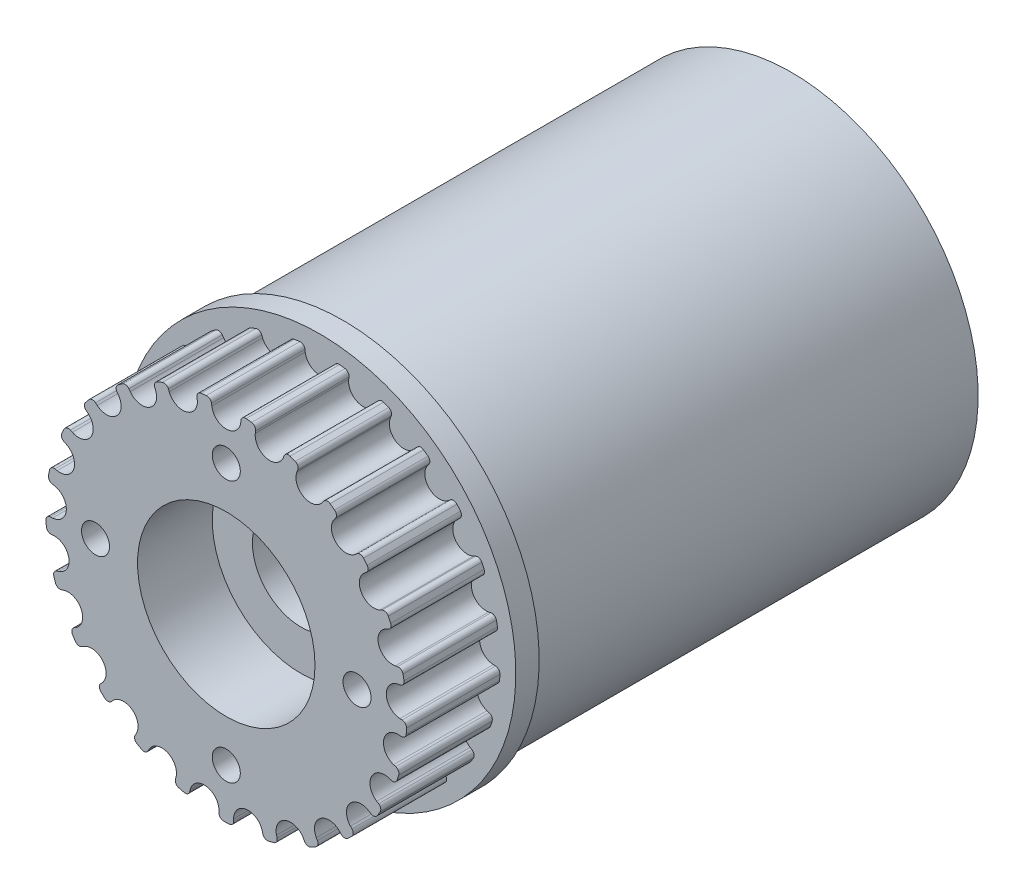
SolidWorks part; units mm, degrees
material "6061 合金"
ref_plane "前视基准面" through (0, 0, 0) normal (0, 0, 1) x (1, 0, 0)
ref_plane "上视基准面" through (0, 0, 0) normal (0, 1, 0) x (1, 0, 0)
ref_plane "右视基准面" through (0, 0, 0) normal (1, 0, 0) x (0, 0, -1)
other "Configuration Table"
sketch "草图1" plane through (0, 0, 0) normal (0, 0, 1) x (1, 0, 0)
  circle A0 centre (0, 0) radius 19.8944
  dimension "P.D" = 39.7887
extrude "凸台-拉伸1" add sketch "草图1" along normal blind 68.5
sketch "草图2" plane through (0, 0, 68.5) normal (0, 0, 1) x (1, 0, 0)
  line L0 (0, 19.8944) -> (0, 19.3224) construction
  line L1 (0, 19.3224) -> (0, 0) construction
  line L2 (1.5774, 18.7687) -> (1.5484, 18.5323)
  line L3 (2.4934, 19.7375) -> (2.4217, 19.17)
  line L4 (-2.4934, 19.7375) -> (-2.4217, 19.17)
  line L5 (-1.5774, 18.7687) -> (-1.5484, 18.5323)
  circle A0 centre (0, 0) radius 19.8944 construction
  arc A1 (2.4934, 19.7375) -> (-2.4934, 19.7375) centre (0, 0) ccw
  circle A2 centre (0, 0) radius 19.3224 construction
  arc A3 (-1.5484, 18.5323) -> (1.5484, 18.5323) centre (0, 18.7224) ccw
  arc A4 (2.1288, 19.2047) -> (2.4217, 19.17) centre (0, 0) cw
  arc A5 (1.5774, 18.7687) -> (2.1288, 19.2047) centre (2.0737, 18.7078) cw
  arc A6 (-1.5774, 18.7687) -> (-2.1288, 19.2047) centre (-2.0737, 18.7078) ccw
  arc A7 (-2.1288, 19.2047) -> (-2.4217, 19.17) centre (0, 0) ccw
  point P16 (1.6369, 19.2529)
  point P21 (0, 17.1624)
  dimension "R" = 1.56
  dimension "D3" = 0.5
  dimension "D1" = 7.2
  dimension "D2" = 7
  dimension "H_g" = 2.16
  dimension "delta" = 0.572
extrude "切除-拉伸1" cut sketch "草图2" against normal through all
pattern_circular "阵列(圆周)1" count 25 over 360 about axis through (0, 0, 68.5) along (0, 0, -1) of "切除-拉伸1" reverse direction yes
ref_plane "基准面1" through (0, 0, 10) normal (0, 0, -1) x (-1, 0, 0)
ref_plane "基准面2" through (0, 0, 11) normal (0, 0, -1) x (-1, 0, 0)
ref_plane "基准面3" through (0, 0, 56) normal (0, 0, -1) x (-1, 0, 0)
ref_plane "基准面4" through (0, 0, 57.5) normal (0, 0, -1) x (-1, 0, 0)
ref_plane "基准面5" through (0, 0, 58.5) normal (0, 0, -1) x (-1, 0, 0)
sketch "草图3" plane through (0, 0, 10) normal (0, 0, -1) x (-1, 0, 0)
  circle A0 centre (0, 0) radius 21
  dimension "D1" = 42
extrude "凸台-拉伸2" add sketch "草图3" against normal up to surface (1 mm away) up to plane "基准面2"
sketch "草图4" plane through (0, 0, 11) normal (0, 0, -1) x (-1, 0, 0)
  circle A0 centre (0, 0) radius 20
  dimension "D1" = 40
extrude "凸台-拉伸3" add sketch "草图4" against normal up to surface (45 mm away) up to plane "基准面3"
sketch "草图5" plane through (0, 0, 56) normal (0, 0, -1) x (-1, 0, 0)
  circle A0 centre (0, 0) radius 21 construction
  circle A1 centre (0, 0) radius 21
extrude "凸台-拉伸4" add sketch "草图5" against normal up to surface (2.5 mm away) up to plane "基准面5"
sketch "草图6" plane through (0, 0, 0) normal (0, 0, -1) x (-1, 0, 0)
  circle A0 centre (0, 0) radius 5.2
  circle A1 centre (0, 0) radius 9.5
  dimension "D1" = 10.4
  dimension "D2" = 19
extrude "切除-拉伸2" cut sketch "草图6" against normal through all contours A0
extrude "切除-拉伸3" cut sketch "草图6<3>" against normal blind 13
sketch "草图6<3>" plane through (0, 0, 0) normal (0, 0, -1) x (-1, 0, 0) same geometry as "草图6"
extrude "切除-拉伸4" cut sketch "草图6<4>" along normal blind 8 from surface starting at face at (-5.2, 0, 68.5)
sketch "草图6<4>" plane through (0, 0, 0) normal (0, 0, -1) x (-1, 0, 0) same geometry as "草图6"
sketch "草图7" plane through (0, 0, 0) normal (0, 0, -1) x (-1, 0, 0)
  circle A0 centre (14, 0) radius 1.5
  circle A1 centre (14, 0) radius 1.5
  circle A2 centre (14, 0) radius 1.5
  circle A3 centre (14, 0) radius 1.5
  circle A4 centre (14, 0) radius 1.5
  circle A5 centre (14, 0) radius 1.5
  circle A6 centre (14, 0) radius 1.5
  circle A7 centre (0, -14) radius 1.5
  circle A8 centre (-14, 0) radius 1.5
  circle A9 centre (0, 14) radius 1.5
  point P4 (0, 0)
  dimension "D1" = 3
  dimension "D2" = 14
  dimension "D5" = 4
  dimension "D4" = 4
  dimension "D3" = 4
extrude "切除-拉伸5" cut sketch "草图7" against normal through all contours A0 | A9 | A8 | A7 region at (-14, 0, 0) region at (0, -14, 0) region at (14, 0, 0) region at (0, 14, 0)
sketch "草图8" plane through (0, 0, 11) normal (0, 0, 1) x (1, 0, 0)
  circle A0 centre (0, 0) radius 21 construction
  circle A1 centre (0, 0) radius 21
extrude "切除-拉伸6" cut sketch "草图8" against normal up to next
sketch "草图9" plane through (0, 0, 13) normal (0, 0, -1) x (-1, 0, 0)
  circle A1 centre (0, 0) radius 9.5
  circle A2 centre (0, 0) radius 9.5
  dimension "D1" = 0
extrude "切除-拉伸7" cut sketch "草图9" against normal blind 6
sketch "草图10" plane through (0, 0, 11) normal (0, 0, -1) x (-1, 0, 0)
  circle A0 centre (0, 0) radius 9.5 construction
  circle A1 centre (0, 0) radius 20
  circle A2 centre (0, 0) radius 20
  circle A3 centre (0, 14) radius 1.5 construction
  circle A4 centre (14, 0) radius 1.5 construction
  circle A5 centre (0, -14) radius 1.5 construction
  circle A6 centre (-14, 0) radius 1.5 construction
  circle A7 centre (-14, 0) radius 1.5
  circle A8 centre (0, -14) radius 1.5
  circle A9 centre (14, 0) radius 1.5
  circle A10 centre (0, 14) radius 1.5
  circle A11 centre (0, 0) radius 9.5
  dimension "D1" = 0
extrude "凸台-拉伸5" add sketch "草图10" along normal blind 3
equation "\"P\"= 5'（勿动）"
equation "\"N\"= 25'齿数（5M不小于13）"
equation "\"H\"= 68.5'齿厚（一般为带宽+2）"
equation "\"R_t\"= 0.5'齿槽圆角（通常无需修改）"
equation "\"P.D@草图1\"= \"P\" * \"N\" / pi'节径"
equation "\"D1@凸台-拉伸1\"=\"H\""
equation "\"D1@草图2\"= 180 / \"N\"'作者：wister"
equation "\"R@草图2\"= 1.56'齿顶圆角"
equation "\"D3@草图2\"=\"R_t\""
equation "\"D1@阵列(圆周)1\"=\"N\""
equation "\"H_g@草图2\"= 2.16'齿槽深"
equation "\"delta@草图2\"= 1.144 / 2'节顶距"
